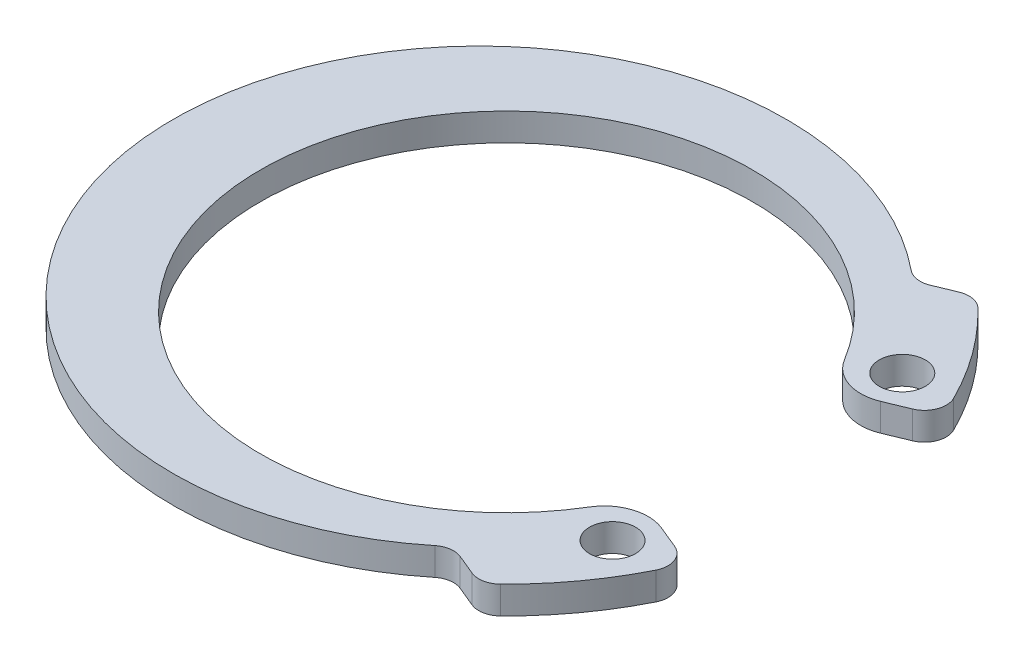
SolidWorks part; units mm, degrees
ref_plane "Front Plane" through (0, 0, 0) normal (0, 0, 1) x (1, 0, 0)
ref_plane "Top Plane" through (0, 0, 0) normal (0, 1, 0) x (1, 0, 0)
ref_plane "Right Plane" through (0, 0, 0) normal (1, 0, 0) x (0, 0, -1)
sketch "Sketch1" plane through (0, 0, 0) normal (0, 1, 0) x (1, 0, 0)
  line L0 (0, 0) -> (3.2569, 4.2444) construction
  line L1 (3.2569, 4.2444) -> (4.4135, 5.7518) construction
  line L2 (0, 0) -> (4.9428, 2.0474) construction
  line L3 (4.9428, 2.0474) -> (6.6981, 2.7745) construction
  line L4 (0, 0) -> (4.9428, -2.0474) construction
  line L5 (4.9428, -2.0474) -> (6.6981, -2.7745) construction
  line L6 (0, 0) -> (3.2569, -4.2444) construction
  line L7 (3.2569, -4.2444) -> (4.4135, -5.7518) construction
  line L8 (5.5558, -4.2631) -> (0, 0) construction
  line L9 (0, 0) -> (7.25, 0) construction
  line L10 (6.6981, 2.7745) -> (6.6981, -2.7745) construction
  line L11 (6.6981, -2.7745) -> (4.4135, -5.7518) construction
  line L12 (6.6981, 2.7745) -> (4.4135, 5.7518) construction
  line L13 (5.5558, 4.2631) -> (0, 0) construction
  line L14 (-5.35, 0) -> (-7.25, 0) construction
  circle A0 centre (0, 0) radius 7.25 construction
  circle A1 centre (0, 0) radius 5.35 construction
  arc A4 (5.8204, 2.4109) -> (4.9981, 3.8352) centre (0, 0) ccw construction
  arc A7 (5.8204, -2.4109) -> (4.9981, -3.8352) centre (0, 0) cw construction
  circle A8 centre (5.456, -3.15) radius 0.5 construction
  circle A9 centre (5.456, 3.15) radius 0.5 construction
  point P20 (6.6981, 0)
  dimension "Ring OD" = 14.5
  dimension "R" = 1
  dimension "D1" = 30
  dimension "D3" = 45
  dimension "S" = 1.9
sketch "Sketch2" plane through (0, 0, 0) normal (1, 0, 0) x (0, 0, -1)
  line L3 (7.25, 0) -> (-7.25, 0) construction
  line L7 (7.25, 0.3) -> (7.25, -0.3) construction
  dimension "Ring Thickness" = 0.6
sketch "Sketch3" plane through (0, 0, 0) normal (0, 1, 0) x (1, 0, 0)
  line L1 (-7.25, 0) -> (-5.35, 0) construction
  line L2 (4.9428, -2.0474) -> (6.6981, -2.7745) construction
  line L3 (3.2569, -4.2444) -> (4.4135, -5.7518) construction
  line L5 (4.1027, 5.1089) -> (4.5453, 5.2923)
  line L6 (5.7539, 2.3833) -> (6.2439, 2.5863)
  line L7 (5.7539, -2.3833) -> (6.2439, -2.5863)
  line L8 (4.1027, -5.1089) -> (4.5453, -5.2923)
  line L9 (3.2569, 4.2444) -> (4.4135, 5.7518) construction
  line L10 (4.9428, 2.0474) -> (6.6981, 2.7745) construction
  line L11 (0, 0) -> (4.9428, 2.0474) construction
  arc A1 (4.5775, 2.7693) -> (4.5775, -2.7693) centre (0, 0) ccw
  circle A2 centre (0, 0) radius 5.35 construction
  arc A3 (3.6217, 5.1789) -> (3.6217, -5.1789) centre (-0.5806, 0) ccw
  circle A4 centre (0, 0) radius 7.25 construction
  arc A6 (5.0585, 5.1937) -> (6.4871, 3.2372) centre (0, 0) cw
  arc A7 (4.5453, -5.2923) -> (5.0585, -5.1937) centre (4.7271, -4.8534) ccw
  arc A8 (5.0585, -5.1937) -> (6.4871, -3.2372) centre (0, 0) ccw
  circle A9 centre (5.456, -3.15) radius 0.5
  circle A10 centre (5.456, 3.15) radius 0.5
  circle A11 centre (5.456, 3.15) radius 0.5 construction
  circle A12 centre (5.456, -3.15) radius 0.5 construction
  arc A13 (3.6217, -5.1789) -> (4.1027, -5.1089) centre (3.921, -5.5478) cw
  arc A14 (6.2439, -2.5863) -> (6.4871, -3.2372) centre (6.0621, -3.0251) cw
  arc A15 (5.7539, -2.3833) -> (4.5775, -2.7693) centre (5.3903, -3.261) ccw
  arc A16 (5.7539, 2.3833) -> (4.5775, 2.7693) centre (5.3903, 3.261) cw
  arc A17 (6.2439, 2.5863) -> (6.4871, 3.2372) centre (6.0621, 3.0251) ccw
  arc A18 (4.5453, 5.2923) -> (5.0585, 5.1937) centre (4.7271, 4.8534) cw
  arc A19 (3.6217, 5.1789) -> (4.1027, 5.1089) centre (3.921, 5.5478) ccw
  arc A20 (5.8204, 2.4109) -> (4.9981, 3.8352) centre (0, 0) ccw construction
  arc A21 (4.9981, -3.8352) -> (5.8204, -2.4109) centre (0, 0) ccw construction
  point P24 (3.8352, 4.9981)
  point P30 (3.8352, -4.9981)
  dimension "D1" = 0.475
  dimension "D2" = 0.95
extrude "Boss-Extrude1" add sketch "Sketch3" along normal up to vertex (0.3 mm away) and the other way up to vertex (0.3 mm away) up to point (0, 0.3, -7.25) other way up to point (0, -0.3, -7.25)
sketch "Sketch4" plane through (0, 0, 0) normal (0, 1, 0) x (1, 0, 0)
  line L0 (0, -6.6441) -> (0, 6.6441) construction
  arc A0 (3.6217, 5.1789) -> (3.6217, -5.1789) centre (-0.5806, 0) ccw construction
  point P7 (0, 0)
  point P9 (0, -6.6441)
sketch "Esquisse1" plane through (0, 0.3, 0) normal (0, 1, 0) x (1, 0, 0)
  circle A0 centre (0, 0) radius 6.5 construction
  dimension "D1" = 13
equation "\"D1@Sketch3\"=\"S@Sketch1\"/4"
equation "\"D2@Sketch3\"=\"S@Sketch1\"/2"
